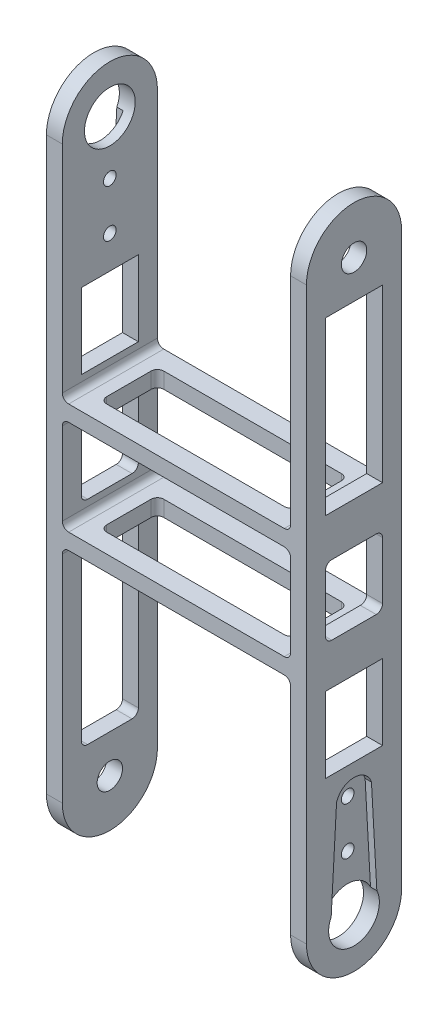
SolidWorks part; units mm, degrees
ref_plane "前视基准面" through (0, 0, 0) normal (0, 0, 1) x (1, 0, 0)
ref_plane "上视基准面" through (0, 0, 0) normal (0, 1, 0) x (1, 0, 0)
ref_plane "右视基准面" through (0, 0, 0) normal (1, 0, 0) x (0, 0, -1)
sketch "草图1" plane through (0, 0, 0) normal (0, 1, 0) x (1, 0, 0)
  line L0 (-16.5, 0) -> (16.5, 0) construction
  point P4 (0, 0)
  dimension "D1" = 33
ref_plane "基准面1" through (18, 0, 0) normal (1, 0, 0) x (0, 0, -1)
ref_plane "基准面2" through (-18, 0, 0) normal (-1, 0, 0) x (0, 0, 1)
sketch "草图4" plane through (-18, 0, 0) normal (-1, 0, 0) x (0, 0, 1)
  line L0 (0, 0) -> (0, -50000) construction
  line L1 (7.5, 90) -> (-7.5, 90) construction
  line L2 (-7.5, 90) -> (-7.5, 0)
  line L3 (-7.5, 0) -> (7.5, 0) construction
  line L4 (7.5, 0) -> (7.5, 90)
  circle A0 centre (0, 0) radius 7.5 construction
  circle A1 centre (0, 90) radius 7.5 construction
  arc A2 (7.5, 90) -> (-7.5, 90) centre (0, 90) ccw
  arc A3 (7.5, 0) -> (-7.5, 0) centre (0, 0) cw
  point P3 (0, 90)
  dimension "D1" = 15
  dimension "D2" = 90
  dimension "D3" = 15
sketch "草图5" plane through (18, 0, 0) normal (1, 0, 0) x (0, 0, -1)
  line L0 (7.5, 0) -> (-7.5, 0) construction
  line L1 (0, 0) -> (0, 29.9674) construction
  line L2 (-7.5, 90) -> (7.5, 90) construction
  line L3 (-7.5, 0) -> (-7.5, 90)
  line L4 (7.5, 90) -> (7.5, 0)
  circle A0 centre (0, 0) radius 7.5 construction
  circle A1 centre (0, 90) radius 7.5 construction
  arc A2 (-7.5, 0) -> (7.5, 0) centre (0, 0) ccw
  arc A3 (-7.5, 90) -> (7.5, 90) centre (0, 90) cw
  point P6 (0, 0)
  point P7 (0, 90)
  point P14 (0, 90)
  dimension "D1" = 15
  dimension "D2" = 90
  dimension "D3" = 15
extrude "凸台-拉伸1" add sketch "草图4" along normal blind 2.5
sketch "草图6" plane through (-20.5, 0, 0) normal (-1, 0, 0) x (0, 0, 1)
  circle A0 centre (0, 0) radius 2
  dimension "D1" = 4
extrude "切除-拉伸1" cut sketch "草图6" against normal blind 3
extrude "凸台-拉伸2" add sketch "草图5" along normal blind 2.5 separate body
sketch "草图7" plane through (20.5, 0, 0) normal (1, 0, 0) x (0, 0, -1)
  line L0 (0, 0) -> (0, 2.3395) construction
  line L1 (3.6, 1.7436) -> (-3.6, 1.7436) construction
  line L2 (-2.75, 17) -> (2.75, 17) construction
  line L3 (-3.6, 1.7436) -> (-2.75, 17)
  line L4 (3.6, 1.7436) -> (2.75, 17)
  circle A0 centre (0, 0) radius 4 construction
  arc A1 (-3.6, 1.7436) -> (3.6, 1.7436) centre (0, 0) ccw
  arc A2 (-2.75, 17) -> (2.75, 17) centre (0, 16.1094) cw
  point P4 (0, 19)
  point P6 (0, 17)
  point P10 (0, 1.7436)
  point P13 (0, 17)
  point P15 (0, -4)
  dimension "D1" = 8
  dimension "D2" = 23
  dimension "D3" = 2
  dimension "D4" = 7.2
  dimension "D5" = 5.5
extrude "切除-拉伸2" cut sketch "草图7" against normal blind 1
sketch "草图8" plane through (19.5, 0, 0) normal (1, 0, 0) x (0, 0, -1)
  line L0 (0, 0) -> (0, 50000) construction
  circle A0 centre (0, 0) radius 4
  circle A1 centre (0, 15.95) radius 1
  circle A2 centre (0, 8.45) radius 1
  point P6 (0, 15.95)
  point P7 (0, 8.45)
  dimension "D1" = 8
  dimension "D3" = 2
  dimension "D5" = 2
  dimension "D2" = 15.95
  dimension "D4" = 7.5
extrude "切除-拉伸3" cut sketch "草图8" against normal up to next
sketch "草图9" plane through (20.5, 0, 0) normal (1, 0, 0) x (0, 0, -1)
  circle A0 centre (0, 90) radius 2
  arc A1 (7.5, 90) -> (-7.5, 90) centre (0, 90) ccw construction
  dimension "D1" = 4
extrude "切除-拉伸4" cut sketch "草图9" against normal up to next
sketch "草图10" plane through (-20.5, 0, 0) normal (-1, 0, 0) x (0, 0, 1)
  line L0 (0, 69.716) -> (0, -49930.284) construction
  line L1 (3.6, 88.2564) -> (-3.6, 88.2564) construction
  line L2 (2.75, 73) -> (-2.75, 73) construction
  line L5 (-2.75, 73) -> (-3.6, 88.2564)
  line L6 (2.75, 73) -> (3.6, 88.2564)
  circle A0 centre (0, 90) radius 4 construction
  arc A1 (7.5, 90) -> (-7.5, 90) centre (0, 90) ccw construction
  arc A3 (3.6, 88.2564) -> (-3.6, 88.2564) centre (0, 90) ccw
  arc A4 (-2.75, 73) -> (2.75, 73) centre (0, 73.8906) ccw
  point P2 (0, 94)
  point P6 (0, 71)
  point P11 (0, 73)
  point P19 (0, 73)
  dimension "D1" = 8
  dimension "D2" = 23
  dimension "D3" = 2
  dimension "D4" = 7.2
  dimension "D5" = 5.5
extrude "切除-拉伸5" cut sketch "草图10" against normal blind 1
sketch "草图11" plane through (-19.5, 0, 0) normal (-1, 0, 0) x (0, 0, 1)
  line L0 (0, 70) -> (0, 62.0556) construction
  circle A0 centre (0, 90) radius 4
  arc A1 (3.6, 88.2564) -> (-3.6, 88.2564) centre (0, 90) ccw construction
  circle A2 centre (0, 74.05) radius 1
  circle A3 centre (0, 81.55) radius 1
  point P6 (0, 81.55)
  point P9 (0, 74.05)
  dimension "D1" = 8
  dimension "D4" = 2
  dimension "D5" = 2
  dimension "D2" = 15.95
  dimension "D3" = 7.5
extrude "切除-拉伸6" cut sketch "草图11" against normal up to next
ref_axis "基准轴1" through (18, 90, 0) along (1, 0, 0)
ref_axis "基准轴2" through (-18, 0, 0) along (-1, 0, 0)
ref_plane "基准面6" through (0, 90, 0) normal (0, 1, 0) x (1, 0, 0)
ref_plane "基准面5" through (0, 45, 0) normal (0, 1, 0) x (1, 0, 0)
sketch "草图12" plane through (0, 0, 0) normal (0, 0, 1) x (1, 0, 0)
  line L0 (18, -55) -> (18, 55) construction
  line L1 (18, 55) -> (-18, 55) construction
  line L2 (18, 55) -> (18, 35) construction
  line L3 (18, 35) -> (-18, 35) construction
  line L4 (-18, 55) -> (-18, 35) construction
  line L5 (18, 55) -> (-18, 35) construction
  line L6 (18, 35) -> (-18, 55) construction
  line L7 (-18, 55) -> (-18, -55) construction
  line L11 (55, 45) -> (-55, 45) construction
  line L12 (18, 55) -> (-18, 55)
  line L13 (18, 55) -> (18, 52.5)
  line L14 (18, 52.5) -> (-18, 52.5)
  line L15 (-18, 55) -> (-18, 52.5)
  line L16 (18, 55) -> (-18, 52.5) construction
  line L17 (18, 52.5) -> (-18, 55) construction
  line L18 (18, 35) -> (-18, 35)
  line L19 (18, 35) -> (18, 37.5)
  line L20 (18, 37.5) -> (-18, 37.5)
  line L21 (-18, 35) -> (-18, 37.5)
  line L22 (18, 35) -> (-18, 37.5) construction
  line L23 (18, 37.5) -> (-18, 35) construction
  point P4 (0, 45)
  point P13 (0, 53.75)
  point P14 (0, 36.25)
  dimension "D2" = 20
  dimension "D3" = 2.5
  dimension "D4" = 2.5
extrude "凸台-拉伸3" add sketch "草图12" along normal up to surface and the other way up to surface up to face at (-19.25, 45, 7.5) other way up to face at (-19.25, 45, -7.5)
sketch "草图13" plane through (-20.5, 0, 0) normal (-1, 0, 0) x (0, 0, 1)
  line L0 (7.5, 0) -> (7.5, 90) construction
  line L1 (4.5, 33) -> (-4.5, 33)
  line L2 (4.5, 33) -> (4.5, 6)
  line L3 (4.5, 6) -> (-4.5, 6)
  line L4 (-4.5, 33) -> (-4.5, 6)
  line L5 (4.5, 33) -> (-4.5, 6) construction
  line L6 (4.5, 6) -> (-4.5, 33) construction
  line L7 (55, 45) -> (-55, 45) construction
  line L8 (4.5, 50.5) -> (-4.5, 50.5)
  line L9 (4.5, 50.5) -> (4.5, 39.5)
  line L10 (4.5, 39.5) -> (-4.5, 39.5)
  line L11 (-4.5, 50.5) -> (-4.5, 39.5)
  line L12 (4.5, 50.5) -> (-4.5, 39.5) construction
  line L13 (4.5, 39.5) -> (-4.5, 50.5) construction
  line L14 (7.5, 55) -> (-7.5, 55) construction
  line L15 (-4.5, 57) -> (4.5, 57)
  line L16 (-4.5, 57) -> (-4.5, 68.8906)
  line L17 (-4.5, 68.8906) -> (4.5, 68.8906)
  line L18 (7.5, 35) -> (-7.5, 35) construction
  line L19 (7.5, 37.5) -> (-7.5, 37.5) construction
  line L20 (4.5, 57) -> (4.5, 68.8906)
  line L21 (-4.5, 57) -> (4.5, 68.8906) construction
  line L22 (-4.5, 68.8906) -> (4.5, 57) construction
  arc A0 (-2.75, 73) -> (2.75, 73) centre (0, 73.8906) ccw construction
  point P4 (0, 19.5)
  point P13 (0, 45)
  point P23 (0, 62.9453)
  dimension "D1" = 7.5
  dimension "D2" = 9
  dimension "D3" = 6
  dimension "D4" = 2
  dimension "D5" = 9
  dimension "D6" = 7.5
  dimension "D7" = 2
  dimension "D8" = 2
  dimension "D9" = 5
  dimension "D10" = 7.5
  dimension "D11" = 9
extrude "切除-拉伸7" cut sketch "草图13" against normal up to surface (20.5 mm away) up to plane "右视基准面"
sketch "草图14" plane through (20.5, 0, 0) normal (1, 0, 0) x (0, 0, -1)
  line L0 (-7.5, 90) -> (-7.5, 0) construction
  line L1 (-4.5, 57) -> (4.5, 57)
  line L2 (-4.5, 57) -> (-4.5, 84)
  line L3 (-4.5, 84) -> (4.5, 84)
  line L4 (4.5, 57) -> (4.5, 84)
  line L5 (-4.5, 57) -> (4.5, 84) construction
  line L6 (-4.5, 84) -> (4.5, 57) construction
  line L7 (-4.5, 39.5) -> (4.5, 39.5)
  line L8 (-4.5, 39.5) -> (-4.5, 50.5)
  line L9 (-4.5, 50.5) -> (4.5, 50.5)
  line L10 (4.5, 39.5) -> (4.5, 50.5)
  line L11 (-4.5, 39.5) -> (4.5, 50.5) construction
  line L12 (-4.5, 50.5) -> (4.5, 39.5) construction
  line L13 (55, 45) -> (-55, 45) construction
  line L14 (-7.5, 55) -> (7.5, 55) construction
  line L15 (-7.5, 52.5) -> (7.5, 52.5) construction
  line L16 (-7.5, 35) -> (7.5, 35) construction
  line L17 (4.5, 33) -> (-4.5, 33)
  line L18 (4.5, 33) -> (4.5, 21.1094)
  line L19 (4.5, 21.1094) -> (-4.5, 21.1094)
  line L20 (-4.5, 33) -> (-4.5, 21.1094)
  line L21 (4.5, 33) -> (-4.5, 21.1094) construction
  line L22 (4.5, 21.1094) -> (-4.5, 33) construction
  arc A0 (2.75, 17) -> (-2.75, 17) centre (0, 16.1094) ccw construction
  point P4 (0, 70.5)
  point P9 (0, 45)
  point P23 (0, 27.0547)
  dimension "D1" = 6
  dimension "D2" = 2
  dimension "D3" = 9
  dimension "D4" = 7.5
  dimension "D5" = 7.5
  dimension "D6" = 9
  dimension "D7" = 2
  dimension "D8" = 7.5
  dimension "D9" = 9
  dimension "D10" = 2
  dimension "D11" = 5
extrude "切除-拉伸8" cut sketch "草图14" against normal up to next and the other way through all
sketch "草图15" plane through (0, 45, 0) normal (0, 1, 0) x (1, 0, 0)
  line L1 (-15, -4.5) -> (15, -4.5)
  line L2 (-15, -4.5) -> (-15, 4.5)
  line L3 (-15, 4.5) -> (15, 4.5)
  line L4 (15, -4.5) -> (15, 4.5)
  line L5 (-15, -4.5) -> (15, 4.5) construction
  line L6 (-15, 4.5) -> (15, -4.5) construction
  line L8 (18, 7.5) -> (-18, 7.5) construction
  point P4 (0, 0)
  dimension "D1" = 3
  dimension "D2" = 30
extrude "切除-拉伸9" cut sketch "草图15" against normal through all both and the other way through all
fillet "圆角1" radius 1 28 edges at (-18, 35, 0) (18, 35, 0) (18, 37.5, 0) (-18, 37.5, 0) (19.25, 39.5, -4.5) (19.25, 50.5, -4.5) (19.25, 50.5, 4.5) (19.25, 39.5, 4.5) (-19.25, 6, -4.5) (-19.25, 6, 4.5) (-19.25, 33, -4.5) (-19.25, 33, 4.5) (-15, 36.25, 4.5) (-15, 36.25, -4.5) (15, 36.25, -4.5) (15, 36.25, 4.5) (-19.25, 50.5, 4.5) (-19.25, 50.5, -4.5) (-19.25, 39.5, -4.5) (-19.25, 39.5, 4.5) (-18, 52.5, 0) (18, 52.5, 0) (15, 53.75, -4.5) (-15, 53.75, -4.5) (-15, 53.75, 4.5) (15, 53.75, 4.5) (18, 55, 0) (-18, 55, 0)
